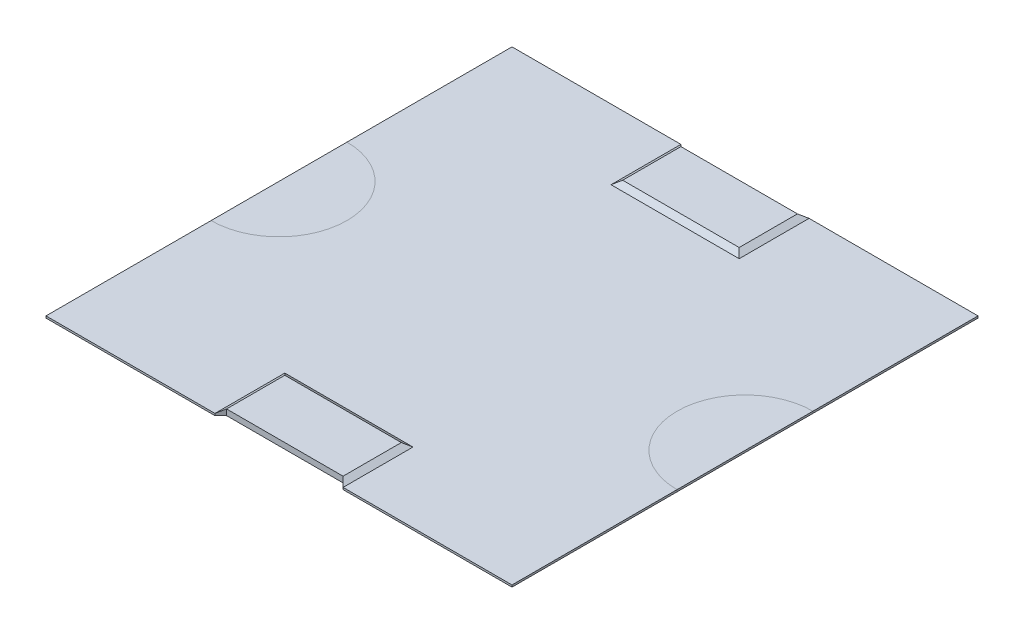
SolidWorks part; units mm, degrees
ref_plane "前视基准面" through (0, 0, 0) normal (0, 0, 1) x (1, 0, 0)
ref_plane "上视基准面" through (0, 0, 0) normal (0, 1, 0) x (1, 0, 0)
ref_plane "右视基准面" through (0, 0, 0) normal (1, 0, 0) x (0, 0, -1)
other "Configuration Table"
sketch "草图1" plane through (0, 0, 0) normal (0, 1, 0) x (1, 0, 0)
  line L0 (1200, 0) -> (1200, 2400) construction
  line L1 (0, 0) -> (2400, 0)
  line L2 (0, 0) -> (0, 2400)
  line L3 (0, 2400) -> (2400, 2400)
  line L4 (2400, 0) -> (2400, 2400)
  line L9 (1200, 2400) -> (1200, 2220) construction
  line L10 (2400, 1200) -> (0, 1200) construction
  line L11 (0, 2400) -> (0, 1550)
  line L12 (870, 0) -> (1530, 0)
  line L13 (900, 2370) -> (1500, 2370)
  line L14 (900, 2370) -> (900, 2070)
  line L15 (900, 2070) -> (1500, 2070)
  line L16 (1500, 2370) -> (1500, 2070)
  line L17 (900, 2370) -> (1500, 2070) construction
  line L18 (900, 2070) -> (1500, 2370) construction
  line L19 (870, 2040) -> (1530, 2040)
  line L20 (870, 2040) -> (870, 2400)
  line L21 (870, 2400) -> (1530, 2400)
  line L22 (1530, 2040) -> (1530, 2400)
  line L23 (870, 2040) -> (1530, 2400) construction
  line L24 (870, 2400) -> (1530, 2040) construction
  line L25 (1530, 360) -> (1530, 0)
  line L26 (870, 360) -> (1530, 360)
  line L27 (870, 360) -> (870, 0)
  line L28 (900, 330) -> (1500, 330)
  line L29 (1500, 30) -> (1500, 330)
  line L30 (900, 30) -> (1500, 30)
  line L31 (900, 30) -> (900, 330)
  line L32 (0, 850) -> (0, 0)
  line L33 (2400, 0) -> (2400, 850)
  line L34 (2400, 2400) -> (2400, 1550)
  arc A0 (0, 850) -> (0, 1550) centre (0, 1200) ccw
  arc A1 (2400, 850) -> (2400, 1550) centre (2400, 1200) cw
  point P8 (0, 2400)
  point P11 (0, 0)
  point P12 (0, 1550)
  point P21 (1200, 180)
  point P34 (0, 0)
  point P35 (0, 0)
  point P36 (0, 0)
  dimension "D7" = 350
  dimension "D1" = 180
  dimension "D2" = 2400
  dimension "D3" = 2400
  dimension "D4" = 300
  dimension "D5" = 300
  dimension "D6" = 30
extrude "凸台-拉伸18" add sketch "草图1<20>" along normal blind 10 separate body contours L4 A1 L3 L22 L19 L20 L2 A0 L1 L27 L26 L25 region at (1200, 0, -1200)
sketch "草图1<20>" plane through (0, 0, 0) normal (0, 1, 0) x (1, 0, 0) same geometry as "草图1"
extrude "凸台-拉伸21" add sketch "草图1<23>" along normal blind 10 separate body contours L2 A0 region at (148.5446, 0, -1200)
sketch "草图1<23>" plane through (0, 0, 0) normal (0, 1, 0) x (1, 0, 0) same geometry as "草图1"
extrude "凸台-拉伸22" add sketch "草图1" along normal blind 10 separate body contours A1 L4 region at (2251.4554, 0, -1200)
extrude "凸台-拉伸24" add sketch "草图1<27>" along normal blind 30 separate body contours L31 L30 L29 L28 region at (1200, 0, -180)
sketch "草图1<27>" plane through (0, 0, 0) normal (0, 1, 0) x (1, 0, 0) same geometry as "草图1"
loft "放样6" add section face at (1530, 5, -180) section face at (1500, 15, -180) connector at (1530, 10, 0) connector at (1500, 30, -30)
loft "放样7" add section face at (900, 15, -180) section face at (870, 5, -180) connector at (900, 30, -30) connector at (870, 10, 0)
loft "放样8" add section face at (1200, 5, -360) section face at (1050, 18.75, -330) connector at (1530, 10, -360) connector at (1500, 30, -330)
extrude "凸台-拉伸25" add sketch "草图1<28>" along normal blind 30 separate body contours L16 L13 L14 L15 region at (1200, 0, -2220)
sketch "草图1<28>" plane through (0, 0, 0) normal (0, 1, 0) x (1, 0, 0) same geometry as "草图1"
loft "放样9" add section face at (870, 5, -2220) section face at (900, 15, -2220) connector at (870, 10, -2040) connector at (900, 30, -2070)
loft "放样10" add section face at (1050, 18.75, -2070) section face at (1200, 5, -2040) connector at (900, 0, -2070) connector at (870, 0, -2040)
loft "放样11" add section face at (1500, 15, -2220) section face at (1530, 5, -2220) connector at (1500, 30, -2070) connector at (1530, 10, -2040)
